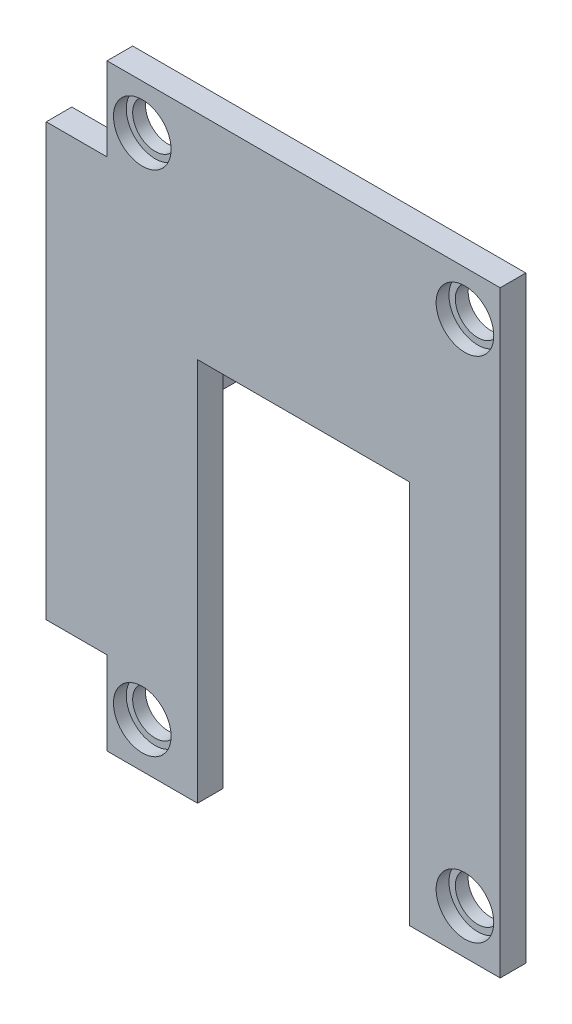
SolidWorks part; units mm, degrees
material "ABS"
ref_plane "Alzado" through (0, 0, 0) normal (0, 0, 1) x (1, 0, 0)
ref_plane "Planta" through (0, 0, 0) normal (0, 1, 0) x (1, 0, 0)
ref_plane "Vista lateral" through (0, 0, 0) normal (1, 0, 0) x (0, 0, -1)
sketch "Croquis1" plane through (0, 0, 0) normal (0, 0, 1) x (1, 0, 0)
  line L0 (0, 93.345) -> (64.3868, 93.345)
  line L1 (0, 93.345) -> (0, 0)
  line L2 (0, 0) -> (64.3868, 0)
  line L3 (64.3868, 93.345) -> (64.3868, 0)
  dimension "D1" = 64.3868
  dimension "D2" = 93.345
extrude "Saliente-Extruir1" add sketch "Croquis1" along normal blind 4
sketch "Croquis2" plane through (0, 0, 4) normal (0, 0, 1) x (1, 0, 0)
  line L5 (0, 0) -> (64.3868, 0) construction
  line L6 (18.63, 0) -> (45.7568, 0)
  line L7 (18.63, 0) -> (18.63, 60)
  line L8 (18.63, 60) -> (45.7568, 60)
  line L9 (45.7568, 0) -> (45.7568, 60)
  line L10 (64.3868, 0) -> (64.3868, 93.345) construction
  line L11 (0, 93.345) -> (0, 0) construction
  dimension "D1" = 18.63
  dimension "D2" = 18.63
  dimension "D3" = 60
extrude "Cortar-Extruir1" cut sketch "Croquis2" against normal through all
sketch "Croquis5" plane through (0, 0, 4) normal (0, 0, 1) x (1, 0, 0)
  line L0 (64.3868, 0) -> (64.3868, 93.345) construction
  line L1 (64.3868, 93.345) -> (0, 93.345) construction
  line L2 (0, 93.345) -> (0, 0) construction
  line L3 (45.7568, 0) -> (64.3868, 0) construction
  circle A0 centre (57.3868, 86.345) radius 4.5
  circle A1 centre (7, 86.345) radius 4.5
  circle A2 centre (57.3868, 7) radius 4.5
  circle A3 centre (7, 7) radius 4.5
  dimension "D5" = 9
  dimension "D1" = 7
  dimension "D2" = 7
  dimension "D3" = 7
  dimension "D4" = 7
  dimension "D6" = 7
extrude "Cortar-Extruir3" cut sketch "Croquis5" against normal blind 2
sketch "Croquis6" plane through (0, 0, 2) normal (0, 0, 1) x (1, 0, 0)
  circle A0 centre (7, 86.345) radius 3.5
  circle A1 centre (57.3868, 86.345) radius 3.5
  circle A2 centre (57.3868, 7) radius 3.5
  circle A3 centre (7, 7) radius 3.5
  dimension "D1" = 7
extrude "Cortar-Extruir4" cut sketch "Croquis6" against normal through all
sketch "Croquis7" plane through (0, 0, 0) normal (0, 0, -1) x (-1, 0, 0)
  line L0 (0, 13) -> (0, 80.345)
  line L3 (0, 13) -> (8, 13)
  line L4 (8, 80.345) -> (8, 13)
  line L5 (0, 93.345) -> (0, 0) construction
  line L6 (0, 80.345) -> (8, 80.345)
  line L7 (-64.3868, 93.345) -> (0, 93.345) construction
  dimension "D1" = 8
  dimension "D2" = 13
  dimension "D3" = 13
extrude "Saliente-Extruir4" add sketch "Croquis7" against normal through all
sketch "Croquis8" plane through (0, 0, 0) normal (0, 0, -1) x (-1, 0, 0)
  line L0 (-18.63, 60) -> (-18.63, 0) construction
  line L1 (8, 80.345) -> (-18.63, 80.345)
  line L2 (8, 80.345) -> (8, 13)
  line L3 (8, 13) -> (-18.63, 13)
  line L4 (-18.63, 80.345) -> (-18.63, 13)
extrude "Saliente-Extruir5" add sketch "Croquis8" against normal blind 2
sketch "Croquis9" plane through (0, 0, 0) normal (0, 0, -1) x (-1, 0, 0)
  line L0 (-64.3868, 93.345) -> (0, 93.345) construction
  line L1 (-63.8868, 93.345) -> (-0.5, 93.345) construction
  line L2 (-63.8868, 93.345) -> (-63.8868, 0)
  line L3 (-63.8868, 0) -> (-0.5, 0) construction
  line L4 (-0.5, 93.345) -> (-0.5, 0) construction
  line L5 (0, 0) -> (-18.63, 0) construction
  line L6 (0, 93.345) -> (0, 80.345) construction
  line L7 (-64.3868, 0) -> (-64.3868, 93.345) construction
  line L8 (-0.5, 93.345) -> (0, 93.345)
  line L9 (0, 93.345) -> (0, 80.345)
  line L10 (0, 80.345) -> (-0.5, 80.345)
  line L11 (-0.5, 0) -> (0, 0)
  line L12 (0, 0) -> (0, 13)
  line L13 (0, 13) -> (-0.5, 13)
  line L14 (8, 13) -> (0, 13) construction
  line L15 (-63.8868, 93.345) -> (-64.3868, 93.345)
  line L16 (-64.3868, 93.345) -> (-64.3868, 0)
  line L17 (-64.3868, 0) -> (-63.8868, 0)
  line L18 (-0.5, 13) -> (-0.5, 0)
  line L19 (-0.5, 80.345) -> (-0.5, 93.345)
  dimension "D1" = 0.5
  dimension "D2" = 0.5
extrude "Cortar-Extruir5" cut sketch "Croquis9" against normal blind 13
sketch "Croquis10" plane through (0, 0, 0) normal (0, 0, -1) x (-1, 0, 0)
  line L0 (8, 80.345) -> (-0.5, 80.345) construction
  line L1 (2, 56.345) -> (7, 56.345)
  line L2 (2, 56.345) -> (2, 36.345)
  line L3 (2, 36.345) -> (7, 36.345)
  line L4 (7, 56.345) -> (7, 36.345)
  line L5 (8, 13) -> (8, 80.345) construction
  dimension "D1" = 24
  dimension "D2" = 20
  dimension "D3" = 1
  dimension "D4" = 5
extrude "Saliente-Extruir6" add sketch "Croquis10" along normal blind 25
fillet "Redondeo1" radius 1 1 edges at (-7, 46.345, 0)
fillet "Redondeo2" radius 5 2 edges at (-5, 56.345, 0) (-5, 36.345, 0)
sketch "Croquis11" plane through (-7, 0, 0) normal (-1, 0, 0) x (0, 0, 1)
  line L0 (-25, 56.345) -> (-5, 56.345) construction
  line L1 (-22, 56.345) -> (0, 56.345) construction
  line L2 (-22, 56.345) -> (-22, 36.345) construction
  line L3 (-22, 36.345) -> (0, 36.345) construction
  line L4 (0, 56.345) -> (0, 36.345) construction
  line L5 (0, 31.345) -> (0, 61.345) construction
  line L6 (-25, 36.345) -> (-5, 36.345) construction
  circle A0 centre (-19.75, 46.345) radius 1.5
  circle A1 centre (-2.25, 46.345) radius 1.5
  point P16 (-22, 46.345)
  dimension "D4" = 3
  dimension "D5" = 3
  dimension "D1" = 22
  dimension "D2" = 17.5
  dimension "D3" = 2.25
extrude "Cortar-Extruir6" cut sketch "Croquis11" against normal through all both and the other way through all
sketch "Croquis12" plane through (0, 0, 0) normal (0, 0, -1) x (-1, 0, 0)
  line L0 (-62.8868, 93.345) -> (-62.8868, 0)
  line L1 (-63.8868, 93.345) -> (-0.5, 93.345) construction
  line L2 (-45.7568, 0) -> (-63.8868, 0) construction
  line L3 (-62.8868, 0) -> (-63.8868, 0)
  line L4 (-63.8868, 0) -> (-63.8868, 93.345)
  line L5 (-63.8868, 93.345) -> (-62.8868, 93.345)
  line L6 (-1.5, 93.345) -> (-0.5, 93.345)
  line L7 (-0.5, 93.345) -> (-0.5, 80.345)
  line L8 (-0.5, 80.345) -> (-1.5, 80.345)
  line L9 (-1.5, 80.345) -> (-1.5, 93.345)
  line L10 (-0.5, 0) -> (-1.5, 0)
  line L11 (-0.5, 0) -> (-18.63, 0) construction
  line L12 (-1.5, 0) -> (-1.5, 13)
  line L13 (-1.5, 13) -> (-0.5, 13)
  line L14 (-45.7568, 0) -> (-45.7568, 60) construction
  line L15 (-46.7568, 0) -> (-17.63, 0)
  line L16 (-46.7568, 0) -> (-46.7568, 60)
  line L17 (-46.7568, 60) -> (-17.63, 60)
  line L18 (-17.63, 0) -> (-17.63, 60)
  line L19 (-18.63, 60) -> (-18.63, 0) construction
  line L20 (-45.7568, 60) -> (-18.63, 60) construction
  line M17 (-45.7568, 0) -> (-45.7568, 60)
  line M18 (-45.7568, 60) -> (-18.63, 60)
  line M19 (-18.63, 60) -> (-18.63, 0)
  line M20 (-18.63, 0) -> (-0.5, 0)
  line M21 (-0.5, 0) -> (-0.5, 13)
  dimension "D1" = 1
  dimension "D2" = 1
  dimension "D3" = 1
  dimension "D4" = 1
  dimension "D5" = 1
extrude "Cortar-Extruir7" cut sketch "Croquis12" against normal through all contours L15 M17 M19 M18 | L13 L12 M20 M21 | L4 L5 L0 L3 | L7 L8 L9 L6 region at (1, 6.5, 0) region at (32.1934, 30, 0)
sketch "Croquis13" plane through (0, 0, -25) normal (0, 0, -1) x (-1, 0, 0)
  line L0 (7, 56.345) -> (2, 56.345) construction
  line L1 (7, 36.345) -> (-13, 36.345)
  line L2 (7, 36.345) -> (7, 56.345)
  line L3 (7, 56.345) -> (-13, 56.345)
  line L4 (-13, 36.345) -> (-13, 56.345)
  dimension "D1" = 20
extrude "Saliente-Extruir7" add sketch "Croquis13" along normal blind 5
sketch "Croquis14" plane through (0, 0, 0) normal (0, 0, -1) x (-1, 0, 0)
  line L0 (-45.7568, 0) -> (-62.8868, 0) construction
  line L1 (-48.7568, 0) -> (-15.63, 0)
  line L2 (-48.7568, 0) -> (-48.7568, 60)
  line L3 (-48.7568, 60) -> (-15.63, 60)
  line L4 (-15.63, 0) -> (-15.63, 60)
  line L5 (-45.7568, 0) -> (-45.7568, 60) construction
  line L6 (-18.63, 60) -> (-18.63, 0) construction
  line L7 (-45.7568, 60) -> (-18.63, 60) construction
  dimension "D1" = 3
  dimension "D2" = 3
extrude "Cortar-Extruir8" cut sketch "Croquis14" against normal blind 10
